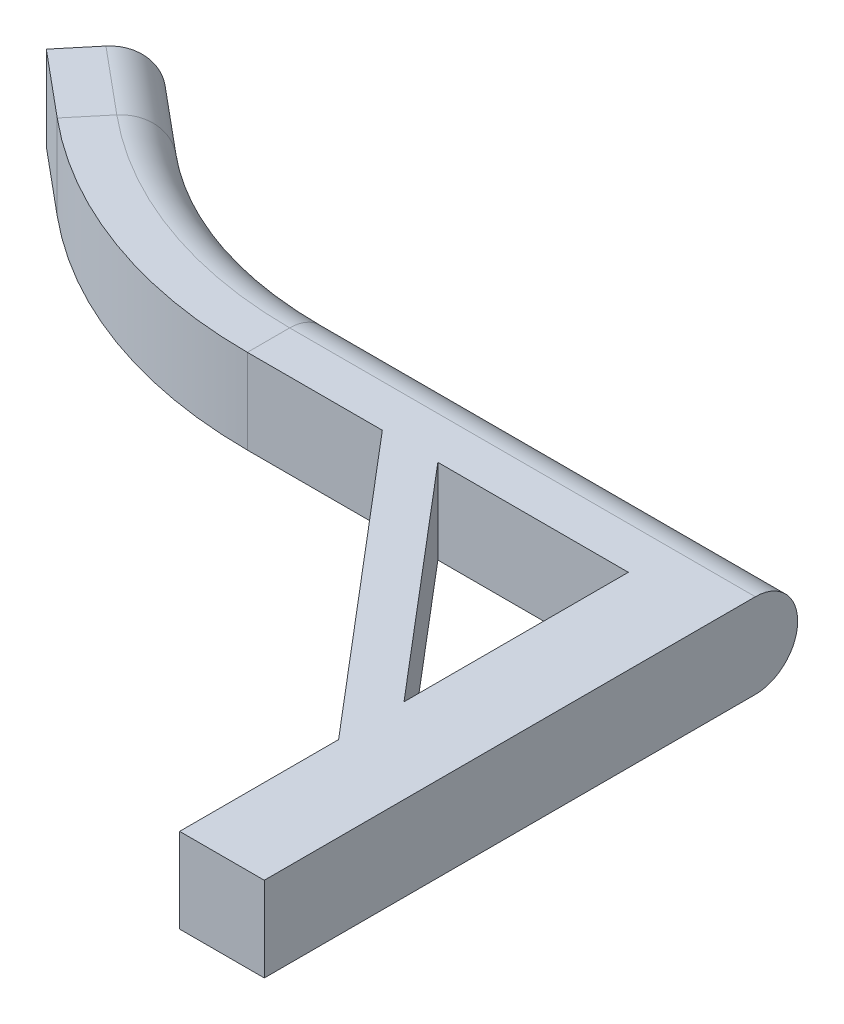
SolidWorks part; units mm, degrees
ref_plane "Front" through (0, 0, 0) normal (0, 0, 1) x (1, 0, 0)
ref_plane "Top" through (0, 0, 0) normal (0, 1, 0) x (1, 0, 0)
ref_plane "Right" through (0, 0, 0) normal (1, 0, 0) x (0, 0, -1)
sketch "Sketch1" plane through (0, 0, 0) normal (0, 1, 0) x (1, 0, 0)
  line L0 (0, 14.5) -> (0, -14.5)
  line L1 (0, 14.5) -> (-25, 14.5)
  line L2 (-41, 20.2906) -> (-44.8419, 23.4906)
  arc A0 (-25, 14.5) -> (-41, 20.2906) centre (-25, 39.5) cw
  point P4 (0, 0)
  point P8 (-20, 35)
  dimension "D3" = 25
  dimension "D1" = 29
  dimension "D2" = 25
  dimension "D4" = 5
  dimension "D5" = 16
ref_plane "Plane1" through (0, 0, 14.5) normal (0, 0, 1) x (1, 0, 0)
sketch "Sketch2" plane through (0, 0, 14.5) normal (0, 0, 1) x (1, 0, 0)
  line L1 (-2.5, 2.5) -> (2.5, 2.5)
  line L2 (-2.5, 2.5) -> (-2.5, -2.5)
  line L3 (-2.5, -2.5) -> (2.5, -2.5)
  line L4 (2.5, 2.5) -> (2.5, -2.5)
  line L5 (-2.5, 2.5) -> (2.5, -2.5) construction
  line L6 (-2.5, -2.5) -> (2.5, 2.5) construction
  point P0 (0, 0)
  dimension "D1" = 5
  dimension "D2" = 5
sweep "Sweep1" add profiles "Sketch2" path "Sketch1"
fillet "Fillet1" radius 2.5 6 edges at (-41.3209, -2.5, -23.8116) (-32.657, -2.5, -18.343) (-41.3209, 2.5, -23.8116) (-32.657, 2.5, -18.343) (-11.25, -2.5, -17) (-11.25, 2.5, -17)
sketch "Sketch3" plane through (0, 2.5, 0) normal (0, 1, 0) x (1, 0, 0)
  line L0 (-17.0296, 12) -> (-2.5, -5.1126)
  line L1 (-2.5, 12) -> (-25, 12) construction
  line L2 (-2.5, -14.5) -> (-2.5, 12) construction
  line L3 (-13.75, 12) -> (-2.5, -1.25)
  line L4 (-17.0296, 12) -> (-13.75, 12)
  line L5 (-2.5, -1.25) -> (-2.5, -5.1126)
  dimension "D1" = 2.5
extrude "Boss-Extrude1" add sketch "Sketch3" against normal up to surface (5 mm away) up to face at (0, -2.5, -2.4)
